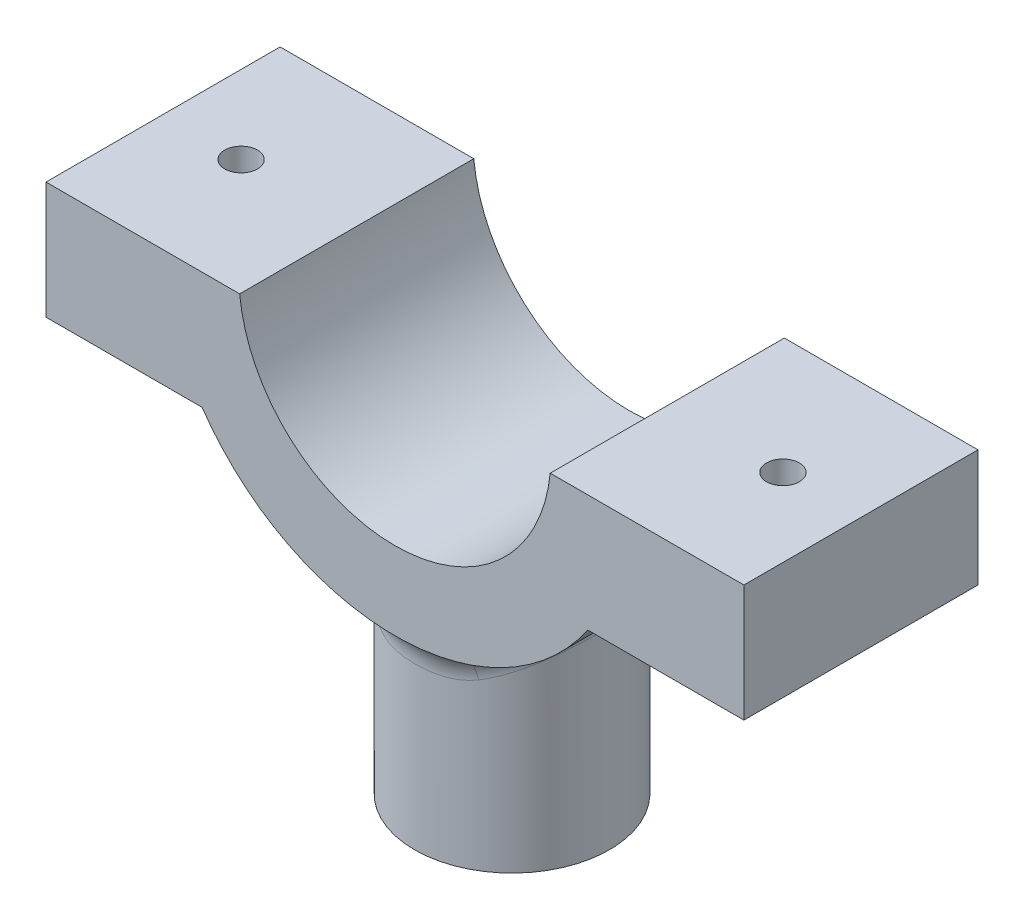
SolidWorks part; units mm, degrees
ref_plane "Plan de face" through (0, 0, 0) normal (0, 0, 1) x (1, 0, 0)
ref_plane "Plan de dessus" through (0, 0, 0) normal (0, 1, 0) x (1, 0, 0)
ref_plane "Plan de droite" through (0, 0, 0) normal (1, 0, 0) x (0, 0, -1)
sketch "Esquisse1" plane through (0, 0, 0) normal (0, 0, 1) x (1, 0, 0)
  line L0 (-19.8997, -2) -> (-44.7184, -2)
  line L1 (-44.7184, -2) -> (-44.7184, -17)
  line L2 (-44.7184, -17) -> (-24.7184, -17)
  line L3 (19.8997, -2) -> (44.7184, -2)
  line L4 (44.7184, -2) -> (44.7184, -17)
  line L5 (44.7184, -17) -> (24.7184, -17)
  line L8 (-44.7184, 2) -> (-44.7184, 17) construction
  line L9 (44.7184, 2) -> (44.7184, 17) construction
  arc A0 (-19.8997, -2) -> (19.8997, -2) centre (0, 0) ccw
  arc A1 (-24.7184, -17) -> (24.7184, -17) centre (0, 0) ccw
  circle A2 centre (0, 0) radius 20 construction
  dimension "D2" = 10
  dimension "D1" = 15
  dimension "D3" = 2
extrude "Boss.-Extru.1" add sketch "Esquisse1" along normal mid plane 30 contours L0 L1 L2 A1 L5 L4 L3 A0
ref_plane "Plan1" through (0, -25, 0) normal (0, 1, 0) x (1, 0, 0)
sketch "Esquisse2" plane through (0, -25, 0) normal (0, 1, 0) x (1, 0, 0)
  circle A0 centre (0, 0) radius 12.5
  dimension "D1" = 25
extrude "Boss.-Extru.2" add sketch "Esquisse2" against normal blind 30
fillet "Congé1" radius 5 1 edges at (-1.7273, -29.9502, -12.3801)
hole_wizard "Trou taraudé M51" positions "Esquisse3" profile "Esquisse4" tap size "M5" standard "ISO" end condition through all
sketch "Esquisse3" plane through (0, -17, 0) normal (0, -1, 0) x (-1, 0, 0)
  line L0 (-44.7184, -15) -> (-24.7184, 15) construction
  line L2 (24.7184, -15) -> (44.7184, 15) construction
  point P0 (-34.7184, 0)
  point P2 (34.7184, 0)
sketch "Esquisse4" plane through (34.7184, -17, 0) normal (1, 0, 0) x (0, 0, -1)
  line L0 (0, 0) -> (0, 15)
  line L1 (0, 15) -> (2.1, 15)
  line L2 (2.1, 15) -> (2.1, 0)
  line L5 (2.1, 0) -> (0, 0)
  line L11 (0, -6.35) -> (0, 107.95) construction
  dimension "Diamètre du trou pour taraudage jusqu'au prochain" = 4.2
  dimension "Profondeur du trou pour taraudage jusqu'au prochain" = 15
cosmetic thread "Filetage de perçage3" parameters "D1"=15, "D2"=5
cosmetic thread "Filetage de perçage4" parameters "D1"=15, "D2"=5
